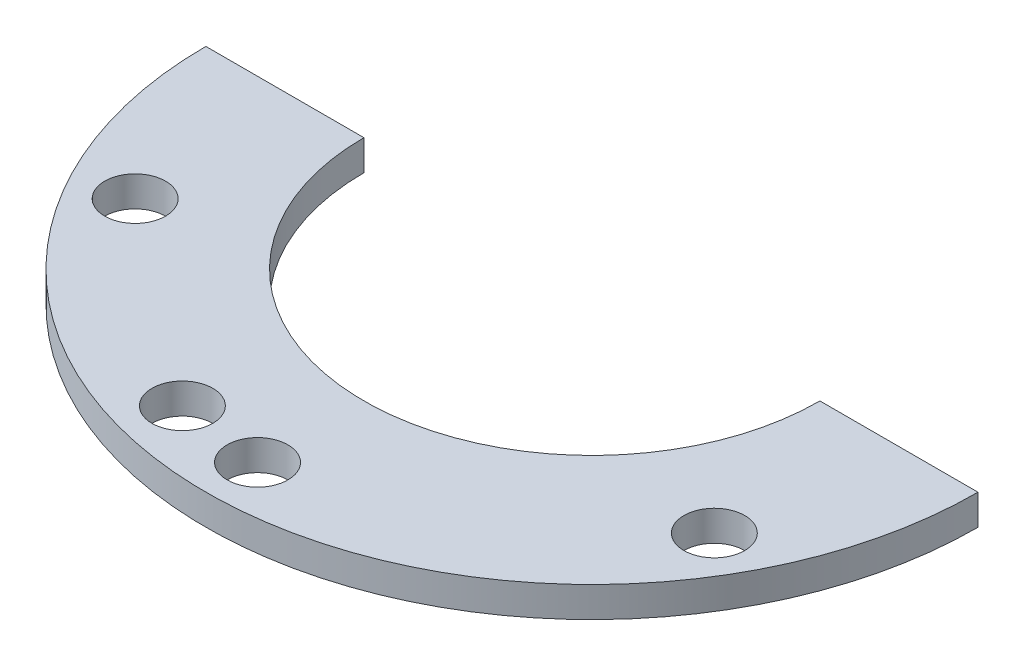
SolidWorks part; units mm, degrees
material "ABS"
ref_plane "Front Plane" through (0, 0, 0) normal (0, 0, 1) x (1, 0, 0)
ref_plane "Top Plane" through (0, 0, 0) normal (0, 1, 0) x (1, 0, 0)
ref_plane "Right Plane" through (0, 0, 0) normal (1, 0, 0) x (0, 0, -1)
sketch "Sketch1" plane through (0, 0, 0) normal (0, 1, 0) x (1, 0, 0)
  circle A0 centre (0, 0) radius 12.7
  dimension "D1" = 25.4
extrude "Boss-Extrude1" add sketch "Sketch1" along normal blind 1
sketch "Sketch19" plane through (0, 1, 0) normal (0, 1, 0) x (1, 0, 0)
  circle A0 centre (0, 11) radius 1
  circle A1 centre (9.5263, 5.5) radius 1
  circle A2 centre (9.5263, -5.5) radius 1
  circle A3 centre (0, -11) radius 1
  circle A4 centre (-9.5263, -5.5) radius 1
  circle A5 centre (-9.5263, 5.5) radius 1
  point P13 (0, 0)
  dimension "D1" = 2
  dimension "D2" = 11
  dimension "D3" = 6
extrude "Cut-Extrude1" cut sketch "Sketch19" against normal through all both and the other way through all
sketch "Sketch20" plane through (0, 1, 0) normal (0, 1, 0) x (1, 0, 0)
  circle A0 centre (0, 0) radius 7.5
  dimension "D1" = 15
extrude "Cut-Extrude2" cut sketch "Sketch20" against normal through all both and the other way through all
sketch "Sketch21" plane through (0, 0, 0) normal (0, 0, 1) x (1, 0, 0)
  line L1 (-36.7533, 32.3113) -> (29.1209, 32.3113)
  line L2 (-36.7533, 32.3113) -> (-36.7533, -19.668)
  line L3 (-36.7533, -19.668) -> (29.1209, -19.668)
  line L4 (29.1209, 32.3113) -> (29.1209, -19.668)
extrude "Cut-Extrude3" cut sketch "Sketch21" against normal through all
sketch "Sketch23" plane through (0, 1, 0) normal (0, 1, 0) x (1, 0, 0)
  line L0 (9.5263, -5.5) -> (0, -11)
  line L1 (0, 0) -> (4.7631, -8.25) construction
  line L2 (4.7631, -8.25) -> (0, 0) construction
  line L3 (0, 0) -> (-4.7287, -17.6476) construction
  circle A0 centre (-2.847, -10.6252) radius 1
  dimension "D1" = 2
  dimension "D2" = 11
  dimension "D3" = 45
extrude "Cut-Extrude4" cut sketch "Sketch23" against normal through all both and the other way through all contours A0 region at (-2.847, 1, 10.6252)
